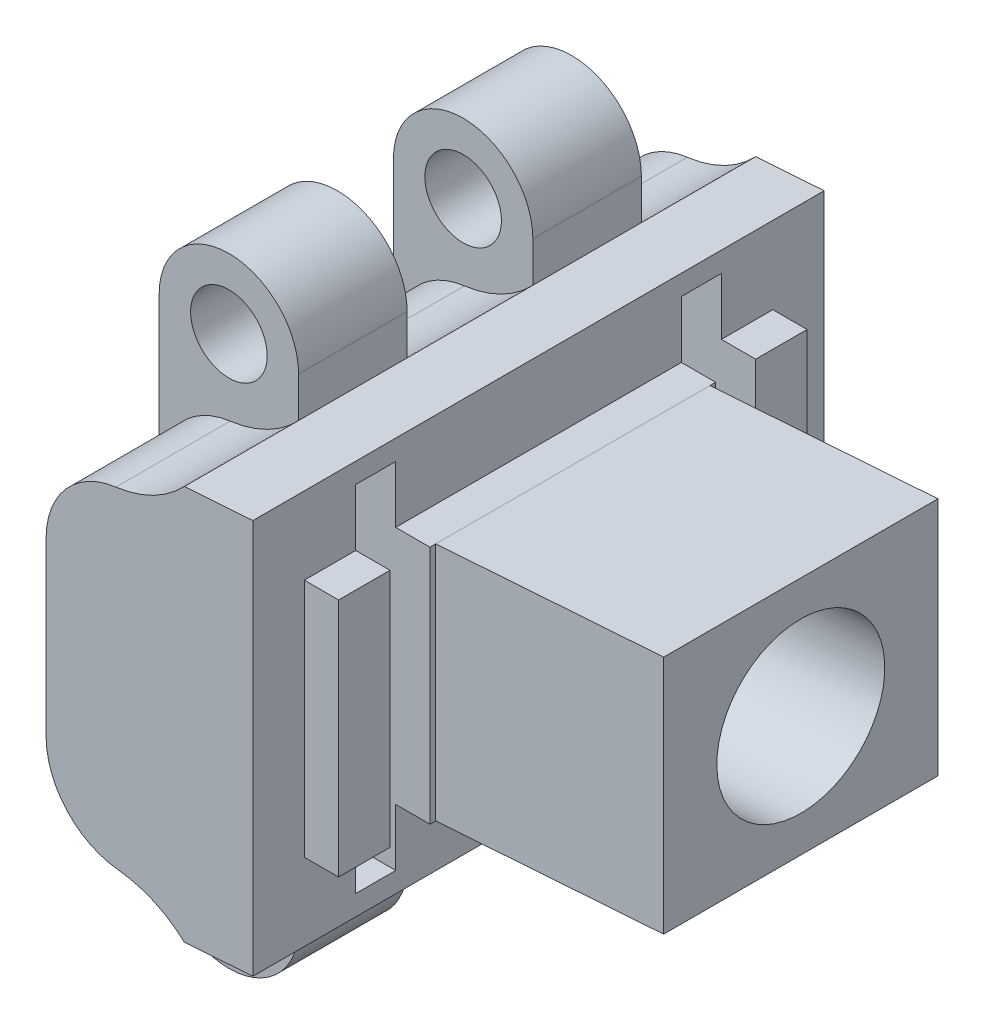
SolidWorks part; units mm, degrees
ref_plane "Front Plane" through (0, 0, 0) normal (0, 0, 1) x (1, 0, 0)
ref_plane "Top Plane" through (0, 0, 0) normal (0, 1, 0) x (1, 0, 0)
ref_plane "Right Plane" through (0, 0, 0) normal (1, 0, 0) x (0, 0, -1)
sketch "Sketch4" plane through (0, 0, 0) normal (0, 0, 1) x (1, 0, 0)
  line L0 (23.1832, 0) -> (-23.1832, 0) construction
  line L1 (7, -14.5) -> (-6, -14.5)
  line L2 (7, -14.5) -> (7, 14.5)
  line L3 (7, 14.5) -> (-6, 14.5)
  line L4 (-6, -14.5) -> (-6, 14.5)
  line L5 (7, -14.5) -> (-6, 14.5) construction
  line L6 (7, 14.5) -> (-6, -14.5) construction
  line L7 (0, -27.5) -> (0, 27.5) construction
  point P0 (0.5, 0)
  dimension "D1" = 6
  dimension "D2" = 7
  dimension "D3" = 29
extrude "Boss-Extrude1" add sketch "Sketch4" along normal blind 50
ref_plane "Plane1" through (0, 0, 14.75) normal (0, 0, 1) x (1, 0, 0)
ref_plane "Plane2" through (0, 0, 25) normal (0, 0, 1) x (1, 0, 0)
sketch "Sketch6" plane through (0, 0, 14.75) normal (0, 0, 1) x (1, 0, 0)
  line L0 (22.6332, 0) -> (-22.6332, 0) construction
  line L1 (0, -27.5) -> (0, 27.5) construction
  line L2 (-6.1, 21) -> (-6.1, 1)
  line L4 (-6.1, 1) -> (6.1, 1)
  line L5 (6.1, 1) -> (6.1, 21)
  circle A0 centre (0, 21) radius 3.35
  arc A1 (6.1, 21) -> (-6.1, 21) centre (0, 21) ccw
  arc A2 (-6.1, 21) -> (6.1, 21) centre (0, 21) ccw construction
  dimension "D1" = 6.7
  dimension "D2" = 12.2
  dimension "D3" = 21
  dimension "D4" = 20
extrude "Boss-Extrude2" add sketch "Sketch6" along normal blind 4.75 and the other way blind 4.75 contours L5 A1 L2 L4 A0 region at (0, 12.4344, 14.75)
mirror "Mirror1" about plane through (0, 0, 25) normal (0, 0, 1) of "Boss-Extrude2"
mirror "Mirror2" about plane through (0, 0, 0) normal (0, 1, 0) of "Mirror1", "Boss-Extrude2"
fillet "Fillet2" radius 7 6 edges at (-6, -14.5, 45) (-6, -14.5, 5) (-6, -14.5, 25) (-6, 14.5, 5) (-6, 14.5, 25) (-6, 14.5, 45)
ref_plane "Plane3" through (6.1, 0, 0) normal (1, 0, 0) x (0, 0, -1)
sketch "Sketch7" plane through (6.1, 0, 0) normal (1, 0, 0) x (0, 0, -1)
  line L0 (22.6332, 0) -> (-22.6332, 0) construction
  line L1 (0, -17.055) -> (-50, -17.055)
  line L2 (0, -17.055) -> (0, 17.055)
  line L3 (0, 17.055) -> (-50, 17.055)
  line L4 (-50, -17.055) -> (-50, 17.055)
  line L5 (0, -17.055) -> (-50, 17.055) construction
  line L6 (0, 17.055) -> (-50, -17.055) construction
  line L7 (-25, 9.955) -> (-25, -9.955) construction
  line L8 (-50, 14.5) -> (0, 14.5) construction
  point P0 (-25, 0)
  dimension "D1" = 34.11
extrude "Boss-Extrude3" add sketch "Sketch7" along normal blind 6
sketch "Sketch8" plane through (0, 0, 50) normal (0, 0, 1) x (1, 0, 0)
  line L0 (6.1, 17.4816) -> (12.1, 17.9011)
  line L1 (0, -27.5) -> (0, 27.5) construction
  line L2 (12.1, 17.9011) -> (12.1, 17.055)
  line L4 (6.1, 17.055) -> (18.7447, 17.055) construction
  line L5 (22.6332, 0) -> (-22.6332, 0) construction
  line L6 (6.1, 17.055) -> (12.1, 17.055)
  line L7 (6.1, 17.055) -> (6.1, 17.4816)
  line L8 (6.1, 14.5) -> (6.1, 17.055) construction
  line L10 (0, 17.055) -> (6.1, 17.4816) construction
  line L11 (0, 17.055) -> (6.1, 17.055) construction
  line L12 (0, 17.055) -> (6.1, 17.055) construction
  dimension "D1" = 4
  dimension "D2" = 17.055
extrude "Boss-Extrude4" add sketch "Sketch8" against normal up to surface (50 mm away) up to face at (3.5701, 0, 0)
sketch "Sketch9" plane through (0, 0, 50) normal (0, 0, 1) x (1, 0, 0)
  line L0 (6.1, -17.055) -> (17.7284, -16.2419)
  line L1 (6.1, -27.5) -> (6.1, 27.5) construction
  line L2 (17.7284, -16.2419) -> (17.7284, -20.1442)
  line L3 (17.7284, -20.1442) -> (6.1, -20.1442)
  line L4 (6.1, -20.1442) -> (6.1, -17.055)
  line L6 (22.6332, 0) -> (-22.6332, 0) construction
  dimension "D1" = 4
  dimension "D2" = 17.055
extrude "Cut-Extrude1" cut sketch "Sketch9" against normal through all
sketch "Sketch10" plane through (12.1, 0, 0) normal (1, 0, 0) x (0, 0, -1)
  line L0 (-25, 9.955) -> (-25, -9.955) construction
  line L1 (0, -16.6354) -> (-50, -16.6354) construction
  line L2 (0, -16.6354) -> (0, 17.9011) construction
  line L3 (0, 17.9011) -> (-50, 17.9011) construction
  line L4 (-50, -16.6354) -> (-50, 17.9011) construction
  line L5 (0, -16.6354) -> (-50, 17.9011) construction
  line L6 (0, 17.9011) -> (-50, -16.6354) construction
  line L7 (0, -16.6354) -> (-50, -16.6354) construction
  line L9 (-4.5, -9.8672) -> (-45.5, -9.8672)
  line L10 (-4.5, -9.8672) -> (-4.5, 11.1328)
  line L11 (-4.5, 11.1328) -> (-45.5, 11.1328)
  line L12 (-45.5, -9.8672) -> (-45.5, 11.1328)
  line L13 (-4.5, -9.8672) -> (-45.5, 11.1328) construction
  line L14 (-4.5, 11.1328) -> (-45.5, -9.8672) construction
  point P0 (-25, 0.6328)
  point P10 (-25, 0.6328)
  dimension "D1" = 41
  dimension "D2" = 21
extrude "Boss-Extrude5" add sketch "Sketch10" along normal blind 3 contours L10 L9 L12 L11
fillet "Fillet4" radius 10 6 edges at (6.1, -14.5, 45) (6.1, -14.5, 25) (6.1, -14.5, 5) (6.1, 14.5, 5) (6.1, 14.5, 25) (6.1, 14.5, 45)
sketch "Sketch11" plane through (12.1, 0, 0) normal (1, 0, 0) x (0, 0, -1)
  line L0 (-25, 9.955) -> (-25, -9.955) construction
  line L1 (0, -16.6354) -> (-50, -16.6354) construction
  line L2 (0, -16.6354) -> (0, 17.9011) construction
  line L3 (0, 17.9011) -> (-50, 17.9011) construction
  line L4 (-50, -16.6354) -> (-50, 17.9011) construction
  line L5 (0, -16.6354) -> (-50, 17.9011) construction
  line L6 (0, 17.9011) -> (-50, -16.6354) construction
  line L7 (0, -16.6354) -> (-50, -16.6354) construction
  line L8 (-9, 16.1328) -> (-12.5, 16.1328)
  line L9 (-41, -14.8672) -> (-37.5, -14.8672)
  line L10 (-41, -14.8672) -> (-41, 16.1328)
  line L11 (-41, 16.1328) -> (-37.5, 16.1328)
  line L12 (-37.5, -14.8672) -> (-37.5, 16.1328)
  line L13 (-41, -14.8672) -> (-37.5, 16.1328) construction
  line L14 (-41, 16.1328) -> (-37.5, -14.8672) construction
  line L15 (-12.5, -14.8672) -> (-12.5, 16.1328)
  line L16 (-9, -14.8672) -> (-12.5, -14.8672)
  line L17 (-9, -14.8672) -> (-9, 16.1328)
  point P0 (-25, 0.6328)
  point P10 (-39.25, 0.6328)
  dimension "D1" = 3.5
  dimension "D2" = 31
  dimension "D3" = 12.5
extrude "Cut-Extrude2" cut sketch "Sketch11" along normal through all and the other way blind 7
sketch "Sketch12" plane through (15.1, 0, 0) normal (1, 0, 0) x (0, 0, -1)
  line L0 (-25, 9.955) -> (-25, -9.955) construction
  line L1 (-12.5, -9.8672) -> (-37.5, -9.8672) construction
  line L2 (-12.5, -9.8672) -> (-12.5, 11.1328) construction
  line L3 (-12.5, 11.1328) -> (-37.5, 11.1328) construction
  line L4 (-37.5, -9.8672) -> (-37.5, 11.1328) construction
  line L5 (-12.5, -9.8672) -> (-37.5, 11.1328) construction
  line L6 (-12.5, 11.1328) -> (-37.5, -9.8672) construction
  line L7 (-12.5, -9.8672) -> (-37.5, -9.8672) construction
  line L9 (-13, -9.8672) -> (-37, -9.8672)
  line L10 (-13, -9.8672) -> (-13, 11.1328)
  line L11 (-13, 11.1328) -> (-37, 11.1328)
  line L12 (-37, -9.8672) -> (-37, 11.1328)
  line L13 (-13, -9.8672) -> (-37, 11.1328) construction
  line L14 (-13, 11.1328) -> (-37, -9.8672) construction
  point P0 (-25, 0.6328)
  point P10 (-25, 0.6328)
  dimension "D1" = 24
sketch "Sketch14" plane through (0, 0, 25) normal (0, 0, 1) x (1, 0, 0)
  line L0 (15.1, 11.1328) -> (34.3064, 12.4759) construction
  line L1 (15.1, -9.8672) -> (15.1, 11.1328) construction
  dimension "D1" = 94
extrude "Boss-Extrude7" add sketch "Sketch12" along direction (0.9976, 0.0698, 0) on the side of the normal blind 20
ref_plane "Plane4" through (35.7525, 2.5001, 0) normal (0.9976, 0.0698, 0) x (0, 0, -1)
sketch "Sketch15" plane through (35.7525, 2.5001, 0) normal (0.9976, 0.0698, 0) x (0, 0, -1)
  line L1 (-25, 9.955) -> (-25, -9.955) construction
  circle A0 centre (-25, -0.3964) radius 7.35
  dimension "D1" = 10.5
  dimension "D2" = 14.7
extrude "Cut-Extrude3" cut sketch "Sketch15" against normal blind 24
